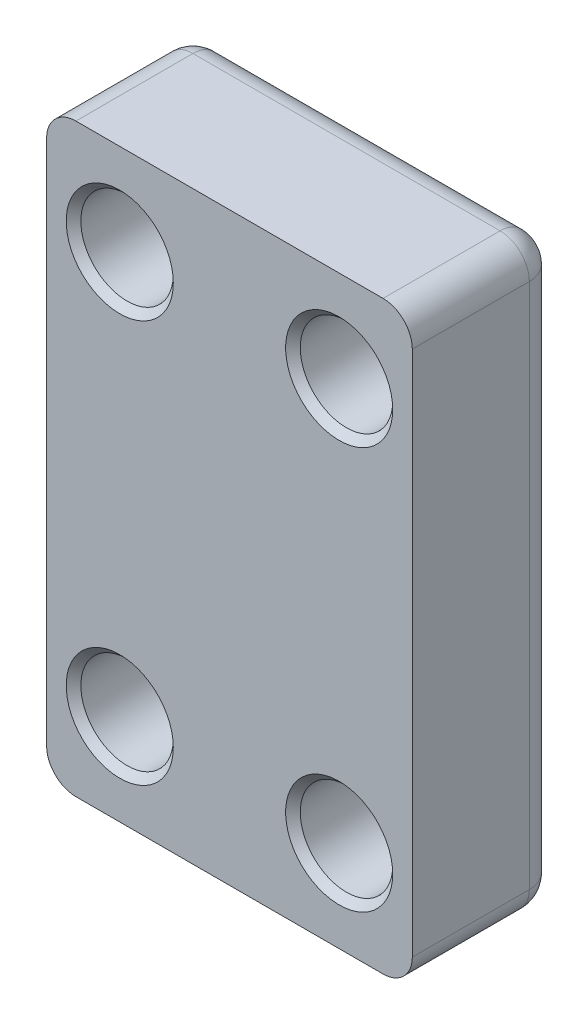
SolidWorks part; units mm, degrees
material "ABS"
ref_plane "Front Plane" through (0, 0, 0) normal (0, 0, 1) x (1, 0, 0)
ref_plane "Top Plane" through (0, 0, 0) normal (0, 1, 0) x (1, 0, 0)
ref_plane "Right Plane" through (0, 0, 0) normal (1, 0, 0) x (0, 0, -1)
sketch "Sketch1" plane through (0, 0, 0) normal (0, 0, 1) x (1, 0, 0)
  line L1 (-15.875, 25.4) -> (15.875, 25.4)
  line L2 (-15.875, 25.4) -> (-15.875, -25.4)
  line L3 (-15.875, -25.4) -> (15.875, -25.4)
  line L4 (15.875, 25.4) -> (15.875, -25.4)
  line L5 (-15.875, 25.4) -> (15.875, -25.4) construction
  line L6 (-15.875, -25.4) -> (15.875, 25.4) construction
  point P0 (0, 0)
  dimension "D1" = 31.75
  dimension "D2" = 50.8
extrude "Boss-Extrude1" add sketch "Sketch1" along normal blind 12.7
hole_wizard "O (0.316) Diameter Hole1" positions "Sketch2" profile "Sketch3" hole size "O" standard "ANSI Inch" end condition up to next
sketch "Sketch2" plane through (0, 0, 12.7) normal (0, 0, 1) x (1, 0, 0)
  line L0 (9.525, -17.4625) -> (-9.525, -17.4625) construction
  line L1 (0, -17.4625) -> (0, 17.4625) construction
  line L2 (9.525, 17.4625) -> (-9.525, 17.4625) construction
  point P0 (-9.525, 17.4625)
  point P2 (9.525, 17.4625)
  point P4 (9.525, -17.4625)
  point P6 (-9.525, -17.4625)
  point P16 (0, 0)
  point P18 (0, 0)
  point P19 (0, 0)
  point P20 (0, 0)
  dimension "D1" = 19.05
  dimension "D2" = 34.925
sketch "Sketch3" plane through (-9.525, 17.4625, 12.7) normal (1, 0, 0) x (0, -1, 0)
  line L0 (0, 0) -> (0, 12.7)
  line L1 (0, 12.7) -> (4.0132, 12.7)
  line L2 (4.0132, 12.7) -> (4.0132, 0.635)
  line L3 (4.0132, 0.635) -> (4.6482, 0)
  line L5 (4.6482, 0) -> (0, 0)
  line L6 (-4.0132, 0.635) -> (-4.6482, 0) construction
  line L11 (0, -6.35) -> (0, 107.95) construction
  dimension "Thru Hole Dia." = 8.0264
  dimension "Thru Hole Depth" = 12.7
  dimension "Near C'Sink Dia." = 9.2964
  dimension "Near C'Sink Angle" = 90
fillet "Fillet1" radius 2.54 12 edges at (-15.875, 25.4, 6.35) (15.875, 25.4, 6.35) (15.875, -25.4, 6.35) (-15.875, -25.4, 6.35) (0, 25.4, 0) (-15.875, 0, 0) (0, -25.4, 0) (15.875, 0, 0) (-5.5118, -17.4625, 0) (13.5382, -17.4625, 0) (13.5382, 17.4625, 0) (-5.5118, 17.4625, 0)
